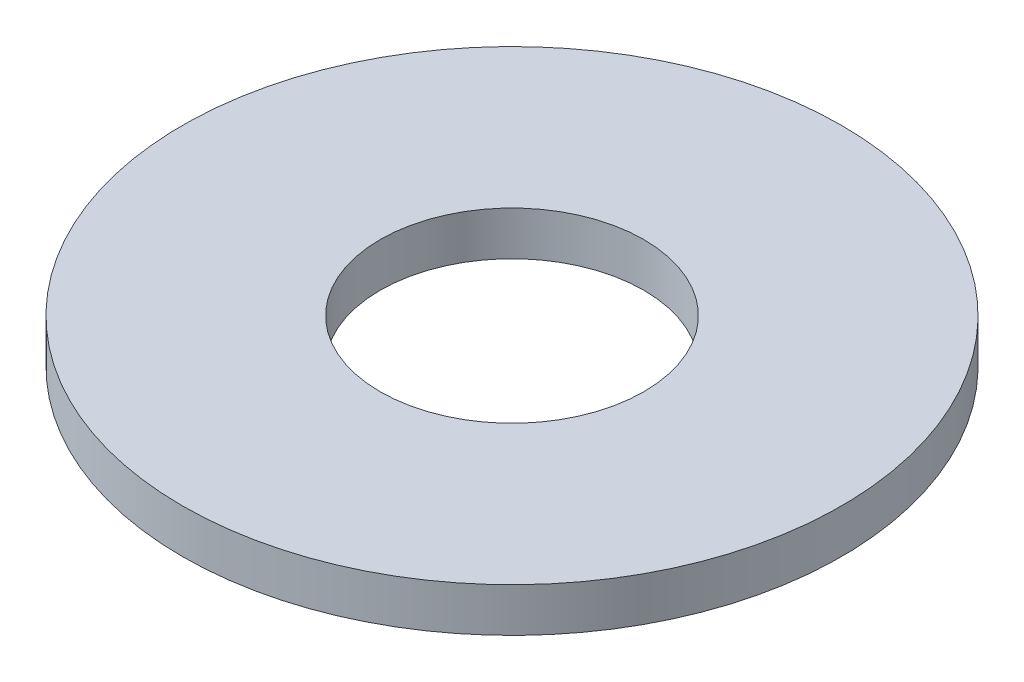
SolidWorks part; units mm, degrees
ref_plane "Front Plane" through (0, 0, 0) normal (0, 0, 1) x (1, 0, 0)
ref_plane "Top Plane" through (0, 0, 0) normal (0, 1, 0) x (1, 0, 0)
ref_plane "Right Plane" through (0, 0, 0) normal (1, 0, 0) x (0, 0, -1)
sketch "Sketch1" plane through (0, 0, 0) normal (0, 1, 0) x (1, 0, 0)
  circle A0 centre (0, 0) radius 75
  dimension "FLANGE_OD" = 150
extrude "Boss-Extrude1" add sketch "Sketch1" along normal blind 10
sketch "Sketch2" plane through (0, 0, 0) normal (0, 1, 0) x (1, 0, 0)
  circle A0 centre (0, 0) radius 30
  dimension "BORE_D" = 60
extrude "Cut-Extrude1" cut sketch "Sketch2" along normal through all
sketch "Sketch3" plane through (0, 10, 0) normal (0, 1, 0) x (1, 0, 0)
  circle A0 centre (0, 0) radius 21.3384 construction
  circle A1 centre (-21.3384, 0) radius 4.8398
  dimension "BOLT_D" = 9.6796
  dimension "BOLT_PCD" = 42.6767
extrude "Cut-Extrude2" cut sketch "Sketch3" against normal blind 6.4761 rebuild error yes
pattern_circular "CirPattern1" count 6 over 360 rebuild error yes
